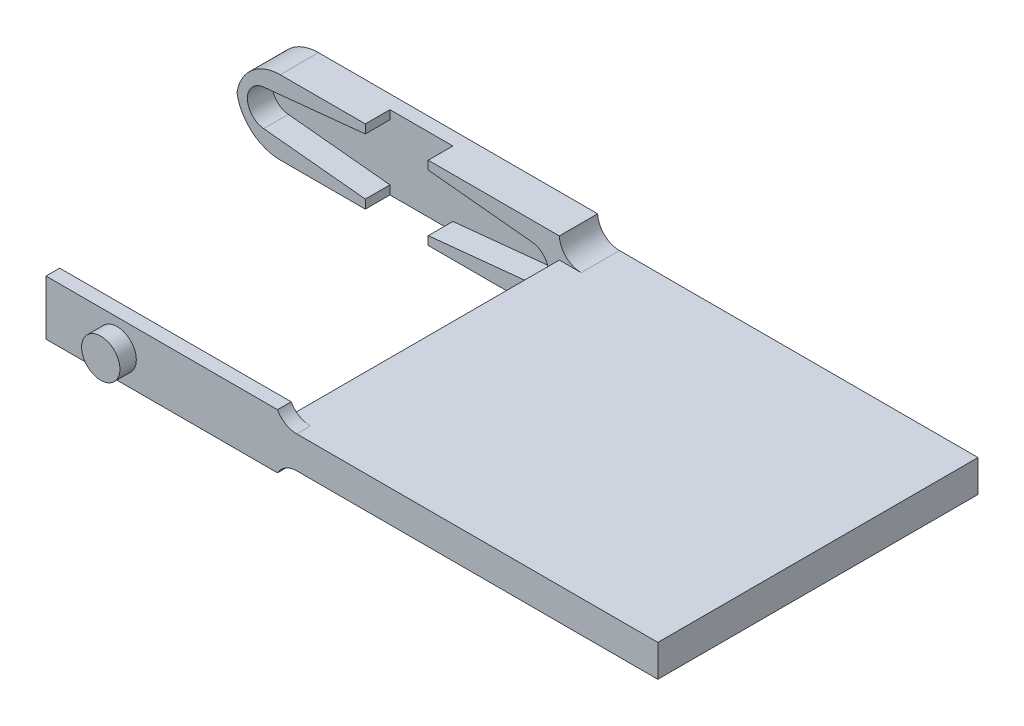
SolidWorks part; units mm, degrees
ref_plane "Front Plane" through (0, 0, 0) normal (0, 0, 1) x (1, 0, 0)
ref_plane "Top Plane" through (0, 0, 0) normal (0, 1, 0) x (1, 0, 0)
ref_plane "Right Plane" through (0, 0, 0) normal (1, 0, 0) x (0, 0, -1)
ref_plane "Ground Plane" through (0, 0, 29.25) normal (0, 0, -1) x (-1, 0, 0)
sketch "Sketch1" plane through (0, 0, 0) normal (0, 0, 1) x (1, 0, 0)
  line L0 (0, 3.375) -> (-13.75, 3.375) construction
  line L1 (0, 3.375) -> (0, 6.25) construction
  line L2 (-12.2651, 5.0167) -> (0, 6.25)
  line L3 (-13.75, 3.375) -> (-13.75, 1.1142) construction
  line L4 (-12.2651, 1.7333) -> (0, 0.5)
  line L5 (12.2651, 1.7333) -> (0, 0.5)
  line L6 (12.2651, 5.0167) -> (0, 6.25)
  line L7 (-2.875, 3.375) -> (-2.875, -5.5898) construction
  line L8 (-14.75, 0) -> (14.75, 0)
  line L9 (-14.75, 0) -> (-14.75, 6.75)
  line L10 (-14.75, 6.75) -> (14.75, 6.75)
  line L12 (13.75, 3.375) -> (13.75, 0.9067) construction
  line L13 (14.75, 4.8371) -> (49.5, 4.8371)
  line L14 (14.5, 4.8371) -> (14.5, 1.9129) construction
  line L15 (14.75, 1.9129) -> (49.5, 1.9129)
  line L16 (49.5, 4.8371) -> (49.5, 1.9129)
  line L18 (14.75, 6.75) -> (14.75, 0)
  circle A0 centre (0, 3.375) radius 2.875 construction
  arc A1 (-12.2651, 5.0167) -> (-12.2651, 1.7333) centre (-12.1, 3.375) ccw
  arc A2 (12.2651, 5.0167) -> (12.2651, 1.7333) centre (12.1, 3.375) cw
  circle A3 centre (-12.1, 3.375) radius 0.2914
  circle A4 centre (-10.0632, 3.375) radius 0.2914
  circle A5 centre (-8.0264, 3.375) radius 0.2914
  circle A6 centre (8.0264, 3.375) radius 0.2914
  circle A7 centre (10.0632, 3.375) radius 0.2914
  circle A8 centre (12.1, 3.375) radius 0.2914
  point P2 (-14.75, 3.375)
  point P27 (0, 6.75)
  point P34 (14.5, 3.375)
  point P35 (49.5, 3.375)
  dimension "D1" = 5.75
  dimension "D9" = 1.65
  dimension "D2" = 3
  dimension "D3" = 2.9241
  dimension "D5" = 29.5
  dimension "D6" = 13.75
  dimension "D7" = 6.75
  dimension "D8" = 1.7333
  dimension "D11" = 27.5
extrude "Boss-Extrude10" add sketch "Sketch1" along normal blind 3.5 contours L6 A2 L14 L10 L9 A1 L2 A0 | A2 L5 A0 L4 A1 L9 L8 region at (-14.4474, 3.375, 0)
extrude "Boss-Extrude15" add sketch "Sketch1<16>" along normal blind 1.25 contours A7 | A8 | A4 | A5 | A3 | L2 A1 L4 A0 A5 A4 A3 | L2 A0 L4 L5 L6 | A2 L6 A0 L5 A7 A6 A8 | A6 | A6 | L6 L2 A1 L4 L5 A2 region at (0, 3.375, 0) region at (-12.1, 3.375, 0) region at (-10.0632, 3.375, 0) region at (-8.0264, 3.375, 0) region at (8.0264, 3.375, 0) region at (10.0632, 3.375, 0) region at (12.1, 3.375, 0)
sketch "Sketch1<16>" plane through (0, 0, 0) normal (0, 0, 1) x (1, 0, 0) same geometry as "Sketch1"
extrude "Boss-Extrude17" add sketch "Sketch1<17>" along direction (0, 0, -1) on the side of the normal up to vertex (29.25 mm away) contours L13 L18 L15 L16 region at (32.125, 3.375, 0)
sketch "Sketch1<17>" plane through (0, 0, 0) normal (0, 0, 1) x (1, 0, 0) same geometry as "Sketch1"
sketch "Sketch2" plane through (0, 0, 29.25) normal (0, 0, 1) x (1, 0, 0)
  line L0 (14.75, 3.375) -> (-6.4, 3.375) construction
  line L1 (14.75, 4.8371) -> (49.5, 4.8371) construction
  line L2 (-6.4, 0.875) -> (14.75, 0.875)
  line L3 (-6.4, 5.875) -> (14.75, 5.875)
  line L4 (-6.4, 5.875) -> (-6.4, 0.875)
  line L5 (14.75, 5.875) -> (14.75, 0.875)
  line L6 (14.75, 4.8371) -> (14.75, 1.9129) construction
  dimension "D1" = 5
  dimension "D2" = 21.15
extrude "Boss-Extrude18" add sketch "Sketch2" against normal blind 1.25 contours L2 L5 L3 L4 | L4 L2 L5 L3 region at (4.175, 3.375, 29.25)
fillet "Fillet1" radius 2 4 edges at (14.75, 4.8371, 28.625) (14.75, 1.9129, 28.625)
fillet "Fillet2" radius 4 2 edges at (-14.75, 6.75, 1.75) (-14.75, 0, 1.75)
sketch "Sketch3" plane through (0, 0, 3.5) normal (0, 0, 1) x (1, 0, 0)
  line L0 (-0.1021, 0) -> (-0.1021, 6.75) construction
  line L1 (-2.9771, 6.75) -> (-2.9771, 0) construction
  line L3 (-10.75, 6.75) -> (14.75, 6.75) construction
  line L4 (-14.7009, 3.375) -> (-0.1021, 3.375) construction
  line L5 (2.7729, 6.75) -> (2.7729, 0) construction
  line L6 (2.7729, 6.75) -> (2.7729, 5.625)
  line L7 (-2.9771, 5.625) -> (2.7729, 5.625)
  line L8 (-2.9771, 0) -> (2.7729, 0)
  line L9 (-2.9771, 0) -> (-2.9771, 1.125)
  line L10 (-2.9771, 1.125) -> (2.7729, 1.125)
  line L11 (2.7729, 0) -> (2.7729, 1.125)
  line L12 (-2.9771, 6.75) -> (2.7729, 6.75)
  line L13 (-2.9771, 6.75) -> (-2.9771, 5.625)
  line L19 (-10.75, 0) -> (14.75, 0) construction
  circle A0 centre (-0.1021, 3.375) radius 2.875 construction
  circle A1 centre (-0.1021, 3.375) radius 2.875 construction
  circle A2 centre (-0.1021, 3.375) radius 2.25 construction
  circle A3 centre (-0.1021, 3.375) radius 2.25 construction
extrude "Cut-Extrude1" cut sketch "Sketch3" against normal up to surface (2.25 mm away)
sketch "Sketch4" plane through (0, 0, 29.25) normal (0, 0, 1) x (1, 0, 0)
  circle A0 centre (0.1021, 3.375) radius 1.75
  circle A1 centre (0.1021, 3.375) radius 2.25 construction
  circle A7 centre (0.1021, 3.375) radius 2.25
  dimension "D1" = 3.5
extrude "Boss-Extrude19" add sketch "Sketch4" along a picked direction on the side of the normal blind 1.5 contours A0
equation "\"D5@Sketch1\"=\"D6@Sketch1\"*2+2"
